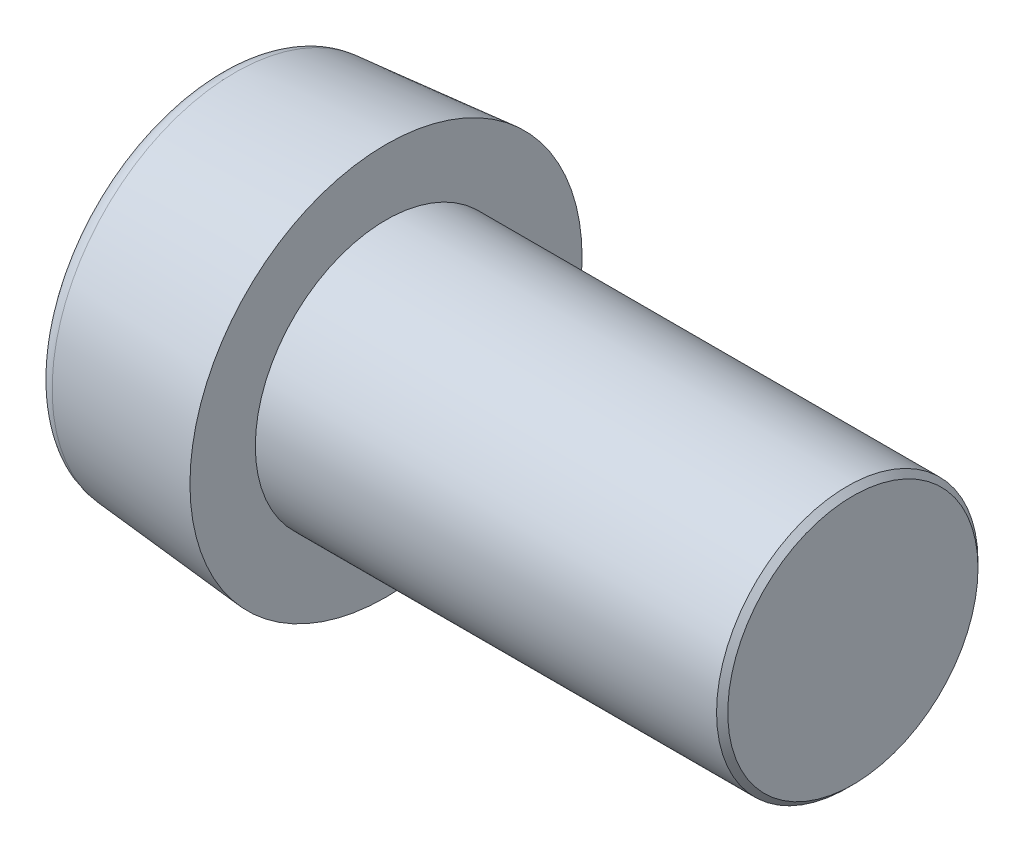
SolidWorks part; units mm, degrees
ref_plane "Front" through (0, 0, 0) normal (0, 0, 1) x (1, 0, 0)
ref_plane "Top" through (0, 0, 0) normal (0, 1, 0) x (1, 0, 0)
ref_plane "Right" through (0, 0, 0) normal (1, 0, 0) x (0, 0, -1)
ref_plane "Plane1" through (9, 0, 0) normal (1, 0, 0) x (0, 0, -1)
sketch "Sketch1" plane through (9, 0, 0) normal (1, 0, 0) x (0, 0, -1)
  circle A0 centre (0, 0) radius 10.5
  dimension "dk" = 21
extrude "BaseHead" add sketch "Sketch1" against normal blind 9 draft 5
sketch "Sketch2" plane through (9, 0, 0) normal (1, 0, 0) x (0, 0, -1)
  circle A0 centre (0, 0) radius 7
extrude "BaseBody" add sketch "Sketch2" along normal blind 25
cosmetic thread "ThreadCosmetic1" parameters "bb"=25, "THD_MINOR"=11.835
fillet "HeadFillet" [suppressed] radius 0.6
sketch "Sketch3" plane through (0, 0, 0) normal (1, 0, 0) x (0, 0, -1)
  line L1 (4.7343, 0) -> (2.3671, 4.1)
  line L2 (2.3671, 4.1) -> (-2.3671, 4.1)
  line L3 (-2.3671, 4.1) -> (-4.7343, 0)
  line L4 (-4.7343, 0) -> (-2.3671, -4.1)
  line L5 (-2.3671, -4.1) -> (2.3671, -4.1)
  line L6 (2.3671, -4.1) -> (4.7343, 0)
  circle A0 centre (0, 0) radius 4.1 construction
  dimension "B" = 8.2
extrude "HexagonSocket" cut sketch "Sketch3" along normal blind 4
sketch "Sketch4" plane through (4, 0, 0) normal (-1, 0, 0) x (0, 0, 1)
  line L0 (2.3671, -4.1) -> (-2.3671, -4.1) construction
  line L1 (-2.3671, -4.1) -> (-4.7343, 0) construction
  line L2 (-4.7343, 0) -> (-2.3671, 4.1) construction
  line L3 (4.7343, 0) -> (2.3671, -4.1) construction
  line L4 (2.3671, 4.1) -> (4.7343, 0) construction
  line L5 (-2.3671, 4.1) -> (2.3671, 4.1) construction
  line L6 (2.3671, -4.1) -> (-2.3671, -4.1)
  line L7 (-2.3671, -4.1) -> (-4.7343, 0)
  line L8 (-4.7343, 0) -> (-2.3671, 4.1)
  line L9 (4.7343, 0) -> (2.3671, -4.1)
  line L10 (2.3671, 4.1) -> (4.7343, 0)
  line L11 (-2.3671, 4.1) -> (2.3671, 4.1)
extrude "Cut-Extrude2" cut sketch "Sketch4" against normal blind 5 draft 60
fillet "TopFillet" radius 1 1 edges at (0, 0, -9.7126)
chamfer "Chamfer1" distance 0.3 angle 45 1 edges at (34, 0, -7)
sketch "Sketch5" plane through (0, 0, 0) normal (0, 0, 1) x (1, 0, 0)
  line L0 (33.7, 6.0625) -> (34.2413, 7)
  line L1 (34.2413, 7) -> (34.2413, 8.0825)
  line L2 (34.2413, 8.0825) -> (33.1588, 8.0825)
  line L3 (33.1588, 8.0825) -> (33.1588, 7)
  line L4 (33.1588, 7) -> (33.7, 6.0625)
  line L5 (0, 0) -> (26.2596, 0) construction
  line L6 (33.7, -7) -> (33.7, 7) construction
  dimension "D1" = 1.0825
  dimension "D2" = 14
revolve "Cut-Revolve10" [suppressed] cut sketch "Sketch5" angle 360 about L5
pattern_linear "LPattern10" [suppressed] count 19 spacing 1.299 along (-1, 0, 0) of bodies 105
equation "\"D1@Plane1\" = \"K@BaseHead\""
equation "\"D2@Sketch5\" = \"d@Sketch2\""
equation "\"D1@Sketch5\" =  ( \"d@Sketch2\" - \"THD_MINOR@ThreadCosmetic1\" )  / 2"
equation "\"D3@LPattern10\" = \"D1@Sketch5\" * 1.2"
equation "\"D1@LPattern10\" = \"bb@ThreadCosmetic1\" / \"D3@LPattern10\""
